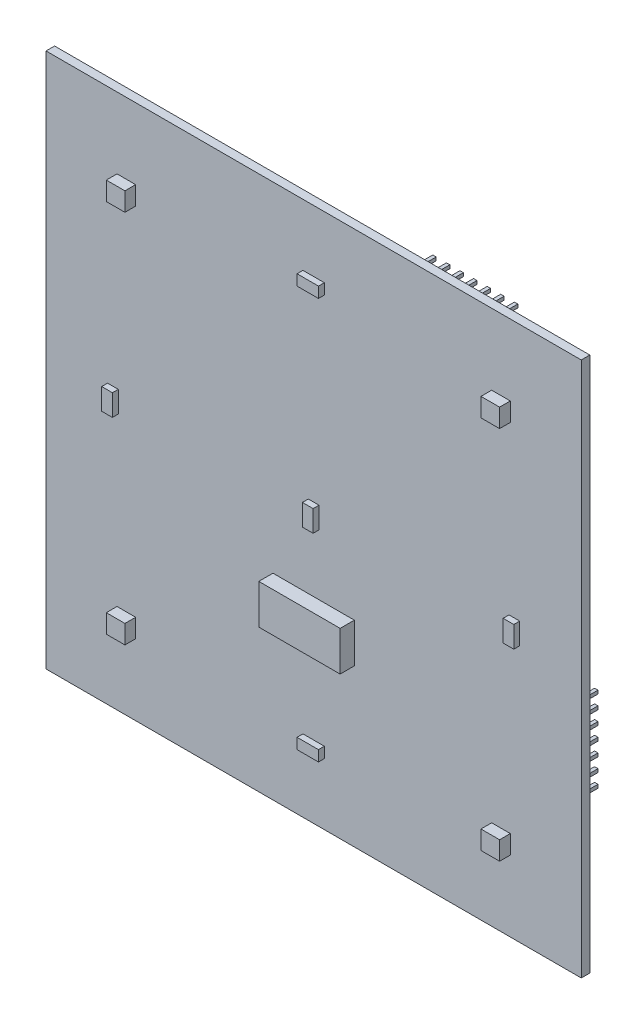
SolidWorks part; units mm, degrees
ref_plane "正面" through (0, 0, 0) normal (0, 0, 1) x (1, 0, 0)
ref_plane "平面" through (0, 0, 0) normal (0, 1, 0) x (1, 0, 0)
ref_plane "右側面" through (0, 0, 0) normal (1, 0, 0) x (0, 0, -1)
sketch "ｽｹｯﾁ1" plane through (0, 0, 0) normal (0, 0, 1) x (1, 0, 0)
  line L0 (-50, 0) -> (50, 0) construction
  line L1 (-50, 50) -> (50, 50)
  line L2 (-50, 50) -> (-50, -50)
  line L3 (-50, -50) -> (50, -50)
  line L4 (50, 50) -> (50, -50)
  line L5 (0, -50) -> (0, 50) construction
  point P8 (0, 0)
  dimension "D1" = 100
  dimension "D2" = 100
  dimension "D3" = 0
  dimension "D4" = 0
extrude "ﾎﾞｽ - 押し出し1" add sketch "ｽｹｯﾁ1" along normal blind 1.6
sketch "ｽｹｯﾁ4" plane through (0, 0, 0) normal (0, 0, -1) x (-1, 0, 0)
  line L0 (-50, -50) -> (-50, 50) construction
  line L1 (11.11, -41.35) -> (28.89, -41.35)
  line L2 (11.11, -41.35) -> (11.11, -43.85)
  line L3 (11.11, -43.85) -> (28.89, -43.85)
  line L4 (28.89, -41.35) -> (28.89, -43.85)
  line L5 (50, -50) -> (-50, -50) construction
  line L6 (50, 50) -> (50, -50) construction
  line L8 (-43.85, -11.11) -> (-41.35, -11.11)
  line L9 (-43.85, -11.11) -> (-43.85, -28.89)
  line L10 (-43.85, -28.89) -> (-41.35, -28.89)
  line L11 (-41.35, -11.11) -> (-41.35, -28.89)
  line L12 (-28.89, 43.85) -> (-11.11, 43.85)
  line L13 (-28.89, 43.85) -> (-28.89, 41.35)
  line L14 (-28.89, 41.35) -> (-11.11, 41.35)
  line L15 (-11.11, 43.85) -> (-11.11, 41.35)
  line L16 (-50, 50) -> (50, 50) construction
  line L18 (41.35, 28.89) -> (43.85, 28.89)
  line L19 (41.35, 28.89) -> (41.35, 11.11)
  line L20 (41.35, 11.11) -> (43.85, 11.11)
  line L21 (43.85, 28.89) -> (43.85, 11.11)
  point P4 (28.89, -42.6)
  point P7 (20, -43.85)
  point P14 (-43.85, -20)
  point P15 (-42.6, -28.89)
  point P22 (-28.89, 42.6)
  point P25 (43.85, 20)
  point P26 (-20, 43.85)
  point P31 (42.6, 28.89)
  dimension "D1" = 7.4
  dimension "D2" = 30
  dimension "D3" = 2.5
  dimension "D4" = 17.78
  dimension "D5" = 2.5
  dimension "D6" = 17.78
  dimension "D7" = 30
  dimension "D8" = 7.4
  dimension "D9" = 2.5
  dimension "D10" = 7.4
  dimension "D11" = 30
  dimension "D12" = 17.78
  dimension "D13" = 17.78
  dimension "D14" = 2.5
  dimension "D15" = 30
  dimension "D16" = 7.4
extrude "ﾎﾞｽ - 押し出し2" add sketch "ｽｹｯﾁ4" along normal blind 2.5
sketch "ｽｹｯﾁ5" plane through (0, 0, -2.5) normal (0, 0, -1) x (-1, 0, 0)
  line L1 (-20.32, 42.92) -> (-19.68, 42.92)
  line L2 (-20.32, 42.92) -> (-20.32, 42.28)
  line L3 (-20.32, 42.28) -> (-19.68, 42.28)
  line L4 (-19.68, 42.92) -> (-19.68, 42.28)
  line L5 (43.85, 28.89) -> (41.35, 28.89) construction
  line L6 (-11.11, 43.85) -> (-28.89, 43.85) construction
  line L7 (-28.89, 43.85) -> (-28.89, 41.35) construction
  line L8 (-43.85, -28.89) -> (-41.35, -28.89) construction
  line L9 (-17.78, 42.92) -> (-17.14, 42.92)
  line L10 (-17.78, 42.92) -> (-17.78, 42.28)
  line L11 (-17.78, 42.28) -> (-17.14, 42.28)
  line L12 (-17.14, 42.92) -> (-17.14, 42.28)
  line L13 (-15.24, 42.92) -> (-14.6, 42.92)
  line L14 (-15.24, 42.92) -> (-15.24, 42.28)
  line L15 (-15.24, 42.28) -> (-14.6, 42.28)
  line L16 (-14.6, 42.92) -> (-14.6, 42.28)
  line L17 (-12.7, 42.92) -> (-12.06, 42.92)
  line L18 (-12.7, 42.92) -> (-12.7, 42.28)
  line L19 (-12.7, 42.28) -> (-12.06, 42.28)
  line L20 (-12.06, 42.92) -> (-12.06, 42.28)
  line L21 (-22.86, 42.92) -> (-22.22, 42.92)
  line L22 (-22.86, 42.92) -> (-22.86, 42.28)
  line L23 (-22.86, 42.28) -> (-22.22, 42.28)
  line L24 (-22.22, 42.92) -> (-22.22, 42.28)
  line L25 (-25.4, 42.92) -> (-24.76, 42.92)
  line L26 (-25.4, 42.92) -> (-25.4, 42.28)
  line L27 (-25.4, 42.28) -> (-24.76, 42.28)
  line L28 (-24.76, 42.92) -> (-24.76, 42.28)
  line L29 (-27.94, 42.92) -> (-27.3, 42.92)
  line L30 (-27.94, 42.92) -> (-27.94, 42.28)
  line L31 (-27.94, 42.28) -> (-27.3, 42.28)
  line L32 (-27.3, 42.92) -> (-27.3, 42.28)
  line L33 (-42.92, -19.68) -> (-42.28, -19.68)
  line L34 (-42.92, -19.68) -> (-42.92, -20.32)
  line L35 (-42.92, -20.32) -> (-42.28, -20.32)
  line L36 (-42.28, -19.68) -> (-42.28, -20.32)
  line L37 (-43.85, -11.11) -> (-43.85, -28.89) construction
  line L38 (43.85, 11.11) -> (43.85, 28.89) construction
  line L39 (-42.92, -22.22) -> (-42.28, -22.22)
  line L40 (-42.92, -22.22) -> (-42.92, -22.86)
  line L41 (-42.92, -22.86) -> (-42.28, -22.86)
  line L42 (-42.28, -22.22) -> (-42.28, -22.86)
  line L44 (42.28, 19.68) -> (42.92, 19.68)
  line L45 (-42.92, -24.76) -> (-42.28, -24.76)
  line L46 (-42.92, -24.76) -> (-42.92, -25.4)
  line L47 (-42.92, -25.4) -> (-42.28, -25.4)
  line L48 (-42.28, -24.76) -> (-42.28, -25.4)
  line L49 (-42.92, -27.3) -> (-42.28, -27.3)
  line L50 (-42.92, -27.3) -> (-42.92, -27.94)
  line L51 (-42.92, -27.94) -> (-42.28, -27.94)
  line L52 (-42.28, -27.3) -> (-42.28, -27.94)
  line L53 (-42.92, -17.14) -> (-42.28, -17.14)
  line L54 (-42.92, -17.14) -> (-42.92, -17.78)
  line L55 (-42.92, -17.78) -> (-42.28, -17.78)
  line L56 (-42.28, -17.14) -> (-42.28, -17.78)
  line L57 (-42.92, -14.6) -> (-42.28, -14.6)
  line L58 (-42.92, -14.6) -> (-42.92, -15.24)
  line L59 (-42.92, -15.24) -> (-42.28, -15.24)
  line L60 (-42.28, -14.6) -> (-42.28, -15.24)
  line L61 (-42.92, -12.06) -> (-42.28, -12.06)
  line L62 (-42.92, -12.06) -> (-42.92, -12.7)
  line L63 (-42.92, -12.7) -> (-42.28, -12.7)
  line L64 (-42.28, -12.06) -> (-42.28, -12.7)
  line L69 (42.28, 19.68) -> (42.28, 20.32)
  line L70 (11.11, -43.85) -> (28.89, -43.85) construction
  line L71 (42.28, 17.78) -> (42.92, 17.78)
  line L72 (42.28, 20.32) -> (42.92, 20.32)
  line L73 (42.92, 19.68) -> (42.92, 20.32)
  line L75 (42.28, 17.78) -> (42.28, 17.14)
  line L76 (42.28, 17.14) -> (42.92, 17.14)
  line L77 (42.92, 17.78) -> (42.92, 17.14)
  line L78 (42.28, 15.24) -> (42.92, 15.24)
  line L79 (42.28, 15.24) -> (42.28, 14.6)
  line L80 (42.28, 14.6) -> (42.92, 14.6)
  line L81 (42.92, 15.24) -> (42.92, 14.6)
  line L82 (42.28, 12.7) -> (42.92, 12.7)
  line L83 (42.28, 12.7) -> (42.28, 12.06)
  line L84 (42.28, 12.06) -> (42.92, 12.06)
  line L85 (42.92, 12.7) -> (42.92, 12.06)
  line L86 (42.28, 22.86) -> (42.92, 22.86)
  line L87 (42.28, 22.86) -> (42.28, 22.22)
  line L88 (42.28, 22.22) -> (42.92, 22.22)
  line L89 (42.92, 22.86) -> (42.92, 22.22)
  line L90 (42.28, 25.4) -> (42.92, 25.4)
  line L91 (42.28, 25.4) -> (42.28, 24.76)
  line L92 (42.28, 24.76) -> (42.92, 24.76)
  line L93 (42.92, 25.4) -> (42.92, 24.76)
  line L94 (42.28, 27.94) -> (42.92, 27.94)
  line L95 (42.28, 27.94) -> (42.28, 27.3)
  line L96 (42.28, 27.3) -> (42.92, 27.3)
  line L97 (42.92, 27.94) -> (42.92, 27.3)
  line L98 (19.68, -42.28) -> (20.32, -42.28)
  line L99 (19.68, -42.28) -> (19.68, -42.92)
  line L100 (19.68, -42.92) -> (20.32, -42.92)
  line L101 (20.32, -42.28) -> (20.32, -42.92)
  line L102 (11.11, -41.35) -> (11.11, -43.85) construction
  line L104 (17.14, -42.28) -> (17.78, -42.28)
  line L105 (17.14, -42.28) -> (17.14, -42.92)
  line L106 (17.14, -42.92) -> (17.78, -42.92)
  line L107 (17.78, -42.28) -> (17.78, -42.92)
  line L108 (14.6, -42.28) -> (15.24, -42.28)
  line L109 (14.6, -42.28) -> (14.6, -42.92)
  line L110 (14.6, -42.92) -> (15.24, -42.92)
  line L111 (15.24, -42.28) -> (15.24, -42.92)
  line L112 (12.06, -42.28) -> (12.7, -42.28)
  line L113 (12.06, -42.28) -> (12.06, -42.92)
  line L114 (12.06, -42.92) -> (12.7, -42.92)
  line L115 (12.7, -42.28) -> (12.7, -42.92)
  line L116 (22.22, -42.28) -> (22.86, -42.28)
  line L117 (22.22, -42.28) -> (22.22, -42.92)
  line L118 (22.22, -42.92) -> (22.86, -42.92)
  line L119 (22.86, -42.28) -> (22.86, -42.92)
  line L120 (24.76, -42.28) -> (25.4, -42.28)
  line L121 (24.76, -42.28) -> (24.76, -42.92)
  line L122 (24.76, -42.92) -> (25.4, -42.92)
  line L123 (25.4, -42.28) -> (25.4, -42.92)
  line L124 (27.3, -42.28) -> (27.94, -42.28)
  line L125 (27.3, -42.28) -> (27.3, -42.92)
  line L126 (27.3, -42.92) -> (27.94, -42.92)
  line L127 (27.94, -42.28) -> (27.94, -42.92)
  point P4 (-20, 42.92)
  point P7 (-20, 43.85)
  point P8 (-20.32, 42.6)
  point P11 (-28.89, 42.6)
  point P16 (-20, 42.28)
  point P17 (-17.46, 42.28)
  point P22 (-14.92, 42.28)
  point P27 (-12.38, 42.28)
  point P40 (-22.54, 42.28)
  point P41 (-25.08, 42.28)
  point P42 (-27.62, 42.28)
  point P47 (-42.6, -20.32)
  point P50 (-42.6, -28.89)
  point P53 (-42.92, -20)
  point P54 (-43.85, -20)
  point P59 (-42.28, -22.54)
  point P60 (-42.28, -20)
  point P61 (-42.28, -25.08)
  point P70 (-42.28, -27.62)
  point P83 (-42.28, -17.46)
  point P84 (-42.28, -14.92)
  point P85 (-42.28, -12.38)
  point P90 (42.6, 19.68)
  point P93 (42.6, 28.89)
  point P94 (42.92, 20)
  point P97 (43.85, 20)
  point P110 (42.28, 12.38)
  point P111 (42.28, 14.92)
  point P112 (42.28, 17.46)
  point P113 (42.28, 20)
  point P126 (42.28, 22.54)
  point P127 (42.28, 25.08)
  point P128 (42.28, 27.62)
  point P133 (20, -42.92)
  point P136 (20, -43.85)
  point P139 (11.11, -42.6)
  point P140 (19.68, -42.6)
  point P165 (17.46, -42.28)
  point P166 (20, -42.28)
  point P167 (14.92, -42.28)
  point P168 (12.38, -42.28)
  point P169 (22.54, -42.28)
  point P170 (25.08, -42.28)
  point P171 (27.62, -42.28)
  point P173 (12.06, -42.6)
  point P174 (14.6, -42.6)
  point P175 (17.14, -42.6)
  point P176 (22.22, -42.6)
  point P177 (24.76, -42.6)
  point P178 (27.3, -42.6)
  point P179 (-42.6, -27.3)
  point P180 (-42.6, -24.76)
  point P181 (-42.6, -22.22)
  point P182 (-42.6, -19.68)
  point P183 (-42.6, -17.14)
  point P184 (-42.6, -14.6)
  point P185 (-42.6, -12.06)
  point P186 (-27.94, 42.6)
  point P187 (-25.4, 42.6)
  point P188 (-22.86, 42.6)
  point P189 (-17.78, 42.6)
  point P190 (-15.24, 42.6)
  point P191 (-12.7, 42.6)
  point P192 (42.6, 15.24)
  point P193 (42.6, 17.78)
  point P194 (42.6, 20.32)
  point P195 (42.6, 22.86)
  point P196 (42.6, 25.4)
  point P197 (42.6, 27.94)
  point P198 (42.6, 12.7)
  dimension "D1" = 0.64
  dimension "D2" = 0.64
  dimension "D3" = 0.64
  dimension "D4" = 0.64
  dimension "D5" = 2.54
  dimension "D6" = 0.64
  dimension "D7" = 2.54
  dimension "D8" = 0.64
  dimension "D9" = 0.64
  dimension "D10" = 0.64
  dimension "D11" = 2.54
  dimension "D12" = 0.64
  dimension "D13" = 0.64
  dimension "D14" = 0.64
  dimension "D15" = 2.54
  dimension "D16" = 0.64
  dimension "D17" = 0.64
  dimension "D18" = 0.64
  dimension "D19" = 2.54
  dimension "D20" = 2.54
  dimension "D21" = 0.64
  dimension "D22" = 0.64
  dimension "D23" = 0.64
  dimension "D24" = 0.64
  dimension "D25" = 2.54
  dimension "D26" = 0.64
  dimension "D27" = 2.54
  dimension "D28" = 0.64
  dimension "D29" = 2.54
  dimension "D30" = 0.64
  dimension "D31" = 0.64
  dimension "D32" = 0.64
  dimension "D33" = 0.64
  dimension "D34" = 2.54
  dimension "D35" = 2.54
  dimension "D36" = 0.64
  dimension "D37" = 0.64
  dimension "D38" = 0.64
  dimension "D39" = 2.54
  dimension "D40" = 0.64
  dimension "D41" = 0.64
  dimension "D42" = 0.64
  dimension "D43" = 0.64
  dimension "D44" = 0.64
  dimension "D45" = 0.64
  dimension "D46" = 2.54
  dimension "D47" = 2.54
  dimension "D48" = 2.54
  dimension "D49" = 2.54
  dimension "D50" = 0.64
  dimension "D51" = 0.64
  dimension "D52" = 0.64
  dimension "D53" = 0.64
  dimension "D54" = 2.54
  dimension "D55" = 0.64
  dimension "D56" = 0.64
  dimension "D57" = 2.54
  dimension "D58" = 0.64
  dimension "D59" = 0.64
  dimension "D60" = 0.64
  dimension "D61" = 0.64
  dimension "D62" = 0.64
  dimension "D63" = 2.54
  dimension "D64" = 2.54
  dimension "D65" = 2.54
  dimension "D66" = 0.64
  dimension "D67" = 0.64
  dimension "D68" = 0.64
  dimension "D69" = 0.64
  dimension "D70" = 0.64
  dimension "D71" = 0.64
  dimension "D72" = 2.54
  dimension "D73" = 2.54
  dimension "D74" = 2.54
  dimension "D75" = 0.64
  dimension "D76" = 0.64
  dimension "D77" = 0.64
  dimension "D78" = 0.64
  dimension "D79" = 0.64
  dimension "D80" = 0.64
extrude "ﾎﾞｽ - 押し出し3" add sketch "ｽｹｯﾁ5" along normal blind 6.1
sketch "ｽｹｯﾁ6" plane through (0, 0, 1.6) normal (0, 0, 1) x (1, 0, 0)
  line L0 (-50, -50) -> (50, -50) construction
  line L1 (-36.74, -33.26) -> (-33.26, -33.26)
  line L2 (-36.74, -33.26) -> (-36.74, -36.74)
  line L3 (-36.74, -36.74) -> (-33.26, -36.74)
  line L4 (-33.26, -33.26) -> (-33.26, -36.74)
  line L5 (-50, 50) -> (-50, -50) construction
  line L6 (50, 50) -> (-50, 50) construction
  line L7 (-36.74, 36.74) -> (-33.26, 36.74)
  line L8 (-36.74, 36.74) -> (-36.74, 33.26)
  line L9 (-36.74, 33.26) -> (-33.26, 33.26)
  line L10 (-33.26, 36.74) -> (-33.26, 33.26)
  line L11 (50, -50) -> (50, 50) construction
  line L12 (33.26, -33.26) -> (36.74, -33.26)
  line L13 (33.26, -33.26) -> (33.26, -36.74)
  line L14 (33.26, -36.74) -> (36.74, -36.74)
  line L15 (36.74, -33.26) -> (36.74, -36.74)
  line L17 (33.26, 36.74) -> (36.74, 36.74)
  line L18 (33.26, 36.74) -> (33.26, 33.26)
  line L19 (33.26, 33.26) -> (36.74, 33.26)
  line L20 (36.74, 36.74) -> (36.74, 33.26)
  point P4 (-36.74, -35)
  point P7 (-35, -36.74)
  point P14 (-36.74, 35)
  point P17 (-35, 36.74)
  point P22 (35, -36.74)
  point P25 (36.74, -35)
  point P30 (35, 36.74)
  point P31 (36.74, 35)
  dimension "D1" = 3.48
  dimension "D2" = 3.48
  dimension "D3" = 15
  dimension "D4" = 15
  dimension "D5" = 3.48
  dimension "D6" = 3.48
  dimension "D7" = 15
  dimension "D8" = 15
  dimension "D9" = 15
  dimension "D10" = 15
  dimension "D11" = 3.48
  dimension "D12" = 3.48
  dimension "D13" = 15
  dimension "D14" = 15
  dimension "D15" = 3.48
  dimension "D16" = 3.48
extrude "ﾎﾞｽ - 押し出し4" add sketch "ｽｹｯﾁ6" along normal blind 2
sketch "ｽｹｯﾁ7" plane through (0, 0, 1.6) normal (0, 0, 1) x (1, 0, 0)
  line L0 (-50, -50) -> (50, -50) construction
  line L1 (-38.5, 2) -> (-36.5, 2)
  line L2 (-38.5, 2) -> (-38.5, -2)
  line L3 (-38.5, -2) -> (-36.5, -2)
  line L4 (-36.5, 2) -> (-36.5, -2)
  line L5 (-50, 50) -> (-50, -50) construction
  line L6 (50, -50) -> (50, 50) construction
  line L7 (36.5, 2) -> (38.5, 2)
  line L8 (36.5, 2) -> (36.5, -2)
  line L9 (36.5, -2) -> (38.5, -2)
  line L10 (38.5, 2) -> (38.5, -2)
  line L11 (50, 50) -> (-50, 50) construction
  line L12 (-2, 38.5) -> (2, 38.5)
  line L13 (-2, 38.5) -> (-2, 36.5)
  line L14 (-2, 36.5) -> (2, 36.5)
  line L15 (2, 38.5) -> (2, 36.5)
  line L17 (-2, -36.5) -> (2, -36.5)
  line L18 (-2, -36.5) -> (-2, -38.5)
  line L19 (-2, -38.5) -> (2, -38.5)
  line L20 (2, -36.5) -> (2, -38.5)
  line L21 (-1, 2) -> (1, 2)
  line L22 (-1, 2) -> (-1, -2)
  line L23 (-1, -2) -> (1, -2)
  line L24 (1, 2) -> (1, -2)
  point P4 (-38.5, 0)
  point P7 (-37.5, -2)
  point P14 (37.5, 2)
  point P17 (38.5, 0)
  point P22 (-2, 37.5)
  point P25 (0, 38.5)
  point P30 (-2, -37.5)
  point P31 (0, -38.5)
  point P36 (1, 0)
  point P37 (36.5, 0)
  point P38 (0, 36.5)
  point P39 (0, 2)
  dimension "D1" = 4
  dimension "D2" = 2
  dimension "D3" = 50
  dimension "D4" = 12.5
  dimension "D5" = 4
  dimension "D6" = 2
  dimension "D7" = 12.5
  dimension "D8" = 50
  dimension "D9" = 4
  dimension "D10" = 2
  dimension "D11" = 12.5
  dimension "D12" = 50
  dimension "D13" = 4
  dimension "D14" = 2
  dimension "D15" = 12.5
  dimension "D16" = 50
  dimension "D17" = 4
  dimension "D18" = 2
extrude "ﾎﾞｽ - 押し出し5" add sketch "ｽｹｯﾁ7" along normal blind 1.1
sketch "ｽｹｯﾁ8" plane through (0, 0, 1.6) normal (0, 0, 1) x (1, 0, 0)
  line L0 (-50, -50) -> (50, -50) construction
  line L1 (-7.6, -13.3) -> (7.6, -13.3)
  line L2 (-7.6, -13.3) -> (-7.6, -20.7)
  line L3 (-7.6, -20.7) -> (7.6, -20.7)
  line L4 (7.6, -13.3) -> (7.6, -20.7)
  point P4 (-7.6, -17)
  point P7 (0, -50)
  point P8 (0, -20.7)
  dimension "D1" = 7.4
  dimension "D2" = 15.2
  dimension "D3" = 33
extrude "ﾎﾞｽ - 押し出し6" add sketch "ｽｹｯﾁ8" along normal blind 2.65
sketch "ｽｹｯﾁ9" plane through (0, 0, 0) normal (0, 0, -1) x (-1, 0, 0)
  line L1 (-4.61, 19.83) -> (3.01, 19.83)
  line L2 (-4.61, 19.83) -> (-4.61, 17.33)
  line L3 (-4.61, 17.33) -> (3.01, 17.33)
  line L4 (3.01, 19.83) -> (3.01, 17.33)
  line L5 (50, 50) -> (50, -50) construction
  line L6 (50, -50) -> (-50, -50) construction
  point P4 (-0.8, 19.83)
  point P7 (3.01, 18.58)
  dimension "D1" = 7.62
  dimension "D2" = 2.5
  dimension "D3" = 50.8
  dimension "D4" = 68.58
extrude "ﾎﾞｽ - 押し出し7" add sketch "ｽｹｯﾁ9" along normal blind 2.5
sketch "ｽｹｯﾁ11" plane through (0, 0, -2.5) normal (0, 0, -1) x (-1, 0, 0)
  line L0 (3.01, 19.83) -> (-4.61, 19.83) construction
  line L1 (-1.12, 18.9) -> (-0.48, 18.9)
  line L2 (-1.12, 18.9) -> (-1.12, 18.26)
  line L3 (-1.12, 18.26) -> (-0.48, 18.26)
  line L4 (-0.48, 18.9) -> (-0.48, 18.26)
  line L5 (-4.61, 19.83) -> (-4.61, 17.33) construction
  line L7 (-3.66, 18.9) -> (-3.02, 18.9)
  line L8 (-3.66, 18.9) -> (-3.66, 18.26)
  line L9 (-3.66, 18.26) -> (-3.02, 18.26)
  line L10 (-3.02, 18.9) -> (-3.02, 18.26)
  line L11 (1.42, 18.9) -> (2.06, 18.9)
  line L12 (1.42, 18.9) -> (1.42, 18.26)
  line L13 (1.42, 18.26) -> (2.06, 18.26)
  line L14 (2.06, 18.9) -> (2.06, 18.26)
  point P4 (-0.8, 18.9)
  point P7 (-0.8, 19.83)
  point P8 (-1.12, 18.58)
  point P11 (-4.61, 18.58)
  point P20 (-3.34, 18.26)
  point P21 (-0.8, 18.26)
  point P22 (1.74, 18.26)
  point P23 (-3.66, 18.58)
  point P24 (1.8193, 18.3224)
  point P25 (1.42, 18.58)
  dimension "D1" = 0.64
  dimension "D2" = 0.64
  dimension "D3" = 0.64
  dimension "D4" = 0.64
  dimension "D5" = 0.64
  dimension "D6" = 2.54
  dimension "D7" = 2.54
extrude "ﾎﾞｽ - 押し出し8" add sketch "ｽｹｯﾁ11" along normal blind 6.1
sketch "ｽｹｯﾁ13" plane through (0, 0, 0) normal (0, 0, -1) x (-1, 0, 0)
  line L0 (-50, -50) -> (-50, 50) construction
  line L7 (-50, 50) -> (50, 50) construction
  line L8 (50, -50) -> (-50, -50) construction
  line L15 (50, 50) -> (50, -50) construction
  line L23 (32, -30) -> (31, -28.2679)
  line L24 (31, -28.2679) -> (29, -28.2679)
  line L25 (29, -28.2679) -> (28, -30)
  line L26 (28, -30) -> (29, -31.7321)
  line L27 (29, -31.7321) -> (31, -31.7321)
  line L28 (31, -31.7321) -> (32, -30)
  line L29 (-28, -30) -> (-29, -28.2679)
  line L30 (-29, -28.2679) -> (-31, -28.2679)
  line L31 (-31, -28.2679) -> (-32, -30)
  line L32 (-32, -30) -> (-31, -31.7321)
  line L33 (-31, -31.7321) -> (-29, -31.7321)
  line L34 (-29, -31.7321) -> (-28, -30)
  line L35 (32, 30) -> (31, 31.7321)
  line L36 (31, 31.7321) -> (29, 31.7321)
  line L37 (29, 31.7321) -> (28, 30)
  line L38 (28, 30) -> (29, 28.2679)
  line L39 (29, 28.2679) -> (31, 28.2679)
  line L40 (31, 28.2679) -> (32, 30)
  line L41 (-28, 30) -> (-29, 31.7321)
  line L42 (-29, 31.7321) -> (-31, 31.7321)
  line L43 (-31, 31.7321) -> (-32, 30)
  line L44 (-32, 30) -> (-31, 28.2679)
  line L45 (-31, 28.2679) -> (-29, 28.2679)
  line L46 (-29, 28.2679) -> (-28, 30)
  circle A0 centre (-30, 30) radius 2 construction
  circle A1 centre (-30, -30) radius 2 construction
  circle A2 centre (30, 30) radius 2 construction
  circle A3 centre (30, -30) radius 2 construction
  point P1 (0, 0)
  dimension "D1" = 20
  dimension "D2" = 20
  dimension "D3" = 20
  dimension "D4" = 20
  dimension "D5" = 20
  dimension "D6" = 20
  dimension "D7" = 20
  dimension "D8" = 20
extrude "ﾎﾞｽ - 押し出し9" add sketch "ｽｹｯﾁ13" along normal blind 6
sketch "ｽｹｯﾁ14" plane through (0, 0, -6) normal (0, 0, -1) x (-1, 0, 0)
  line L2 (0, -39) -> (0, -41)
  line L3 (0, -41) -> (39, -41)
  line L4 (39, -41) -> (39, 0)
  line L5 (39, 0) -> (41, 0)
  line L6 (41, 0) -> (41, 39)
  line L7 (41, 39) -> (0, 39)
  line L8 (0, 39) -> (0, 41)
  line L9 (0, 41) -> (-39, 41)
  line L11 (-39, 41) -> (-39, 0)
  line L12 (-39, 0) -> (-41, 0)
  line L13 (-41, 0) -> (-41, -39)
  line L14 (-41, -39) -> (0, -39)
  line L21 (-29, 31.7321) -> (-31, 31.7321) construction
  line L22 (-4.61, 19.83) -> (3.01, 19.83)
  line L23 (-4.61, 19.83) -> (-4.61, 17.33)
  line L24 (-4.61, 17.33) -> (3.01, 17.33)
  line L25 (3.01, 19.83) -> (3.01, 17.33)
  line L26 (31, 31.7321) -> (29, 31.7321) construction
  line L27 (31, -28.2679) -> (29, -28.2679) construction
  line L28 (-29, -28.2679) -> (-31, -28.2679) construction
  circle A0 centre (-30, 30) radius 1
  circle A1 centre (30, 30) radius 1
  circle A2 centre (30, -30) radius 1
  circle A3 centre (-30, -30) radius 1
  point P25 (0, 0)
  point P28 (-30, 31.7321)
  point P37 (30, 31.7321)
  point P41 (30, -28.2679)
  point P47 (-30, -28.2679)
  point P48 (0, 0)
  dimension "D1" = 39
  dimension "D2" = 41
  dimension "D3" = 41
  dimension "D4" = 39
  dimension "D5" = 41
  dimension "D6" = 39
  dimension "D7" = 41
  dimension "D8" = 39
  dimension "D9" = 2.5
  dimension "D10" = 7.62
extrude "ﾎﾞｽ - 押し出し10" add sketch "ｽｹｯﾁ14" along normal blind 2
